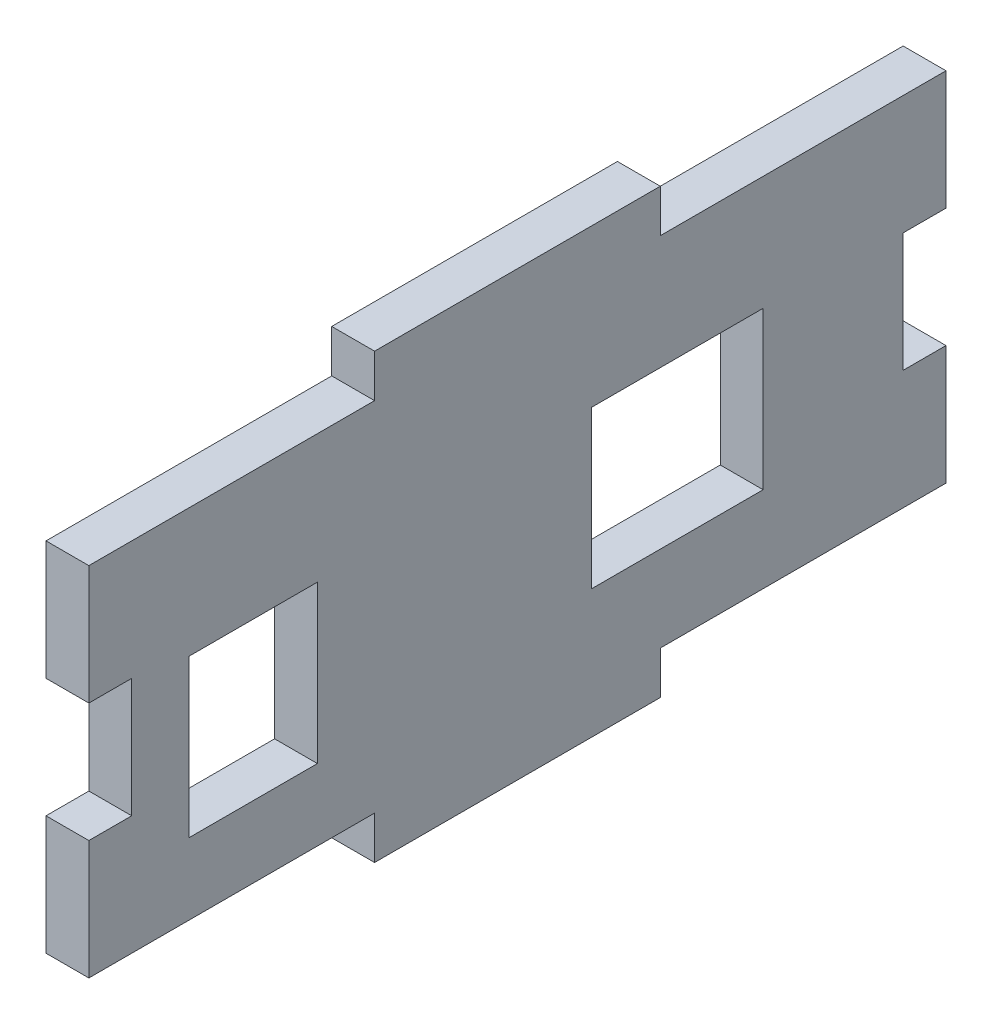
SolidWorks part; units mm, degrees
ref_plane "Front Plane" through (0, 0, 0) normal (0, 0, 1) x (1, 0, 0)
ref_plane "Top Plane" through (0, 0, 0) normal (0, 1, 0) x (1, 0, 0)
ref_plane "Right Plane" through (0, 0, 0) normal (1, 0, 0) x (0, 0, -1)
sketch "Sides" plane through (0, 0, 0) normal (1, 0, 0) x (0, 0, -1)
  line L0 (0, 16.6667) -> (0, 25)
  line L1 (0, 0) -> (20, 0)
  line L2 (0, 0) -> (0, 8.3333)
  line L3 (0, 25) -> (20, 25)
  line L4 (60, 0) -> (60, 8.34)
  line L5 (0, 16.6667) -> (3, 16.6667)
  line L6 (40, 25) -> (60, 25)
  line L7 (0, 8.3333) -> (3, 8.3333)
  line L8 (3, 16.6667) -> (3, 8.3333)
  line L9 (40, 0) -> (60, 0)
  line L10 (20, 25) -> (20, 28)
  line L11 (20, 28) -> (40, 28)
  line L12 (40, 25) -> (40, 28)
  line L13 (60, 16.67) -> (60, 25)
  line L14 (40, 0) -> (40, -3)
  line L15 (20, 0) -> (20, -3)
  line L16 (20, -3) -> (40, -3)
  line L17 (60, 16.67) -> (57, 16.67)
  line L18 (60, 8.34) -> (57, 8.34)
  line L19 (57, 16.67) -> (57, 8.34)
  line L21 (47.2, 17) -> (35.2, 17)
  line L22 (47.2, 17) -> (47.2, 6)
  line L23 (47.2, 6) -> (35.2, 6)
  line L24 (35.2, 17) -> (35.2, 6)
  line L25 (16, 16) -> (7, 16)
  line L26 (16, 16) -> (16, 5)
  line L27 (16, 5) -> (7, 5)
  line L28 (7, 16) -> (7, 5)
  dimension "D1" = 25
  dimension "D2" = 60
  dimension "D3" = 8.3333
  dimension "D4" = 8.3333
  dimension "D5" = 3
  dimension "D6" = 20
  dimension "D7" = 3
  dimension "D8" = 20
  dimension "D9" = 11
  dimension "D10" = 12
  dimension "D11" = 11
  dimension "D12" = 9
  dimension "D13" = 19.2
  dimension "D14" = 4
  dimension "D15" = 9.8
  dimension "D16" = 20
  dimension "D17" = 20
  dimension "D18" = 1
  dimension "D19" = 5
  dimension "D20" = 3
  dimension "D21" = 8.33
  dimension "D22" = 8.33
extrude "Sides Extruded" add sketch "Sides" along normal blind 3
